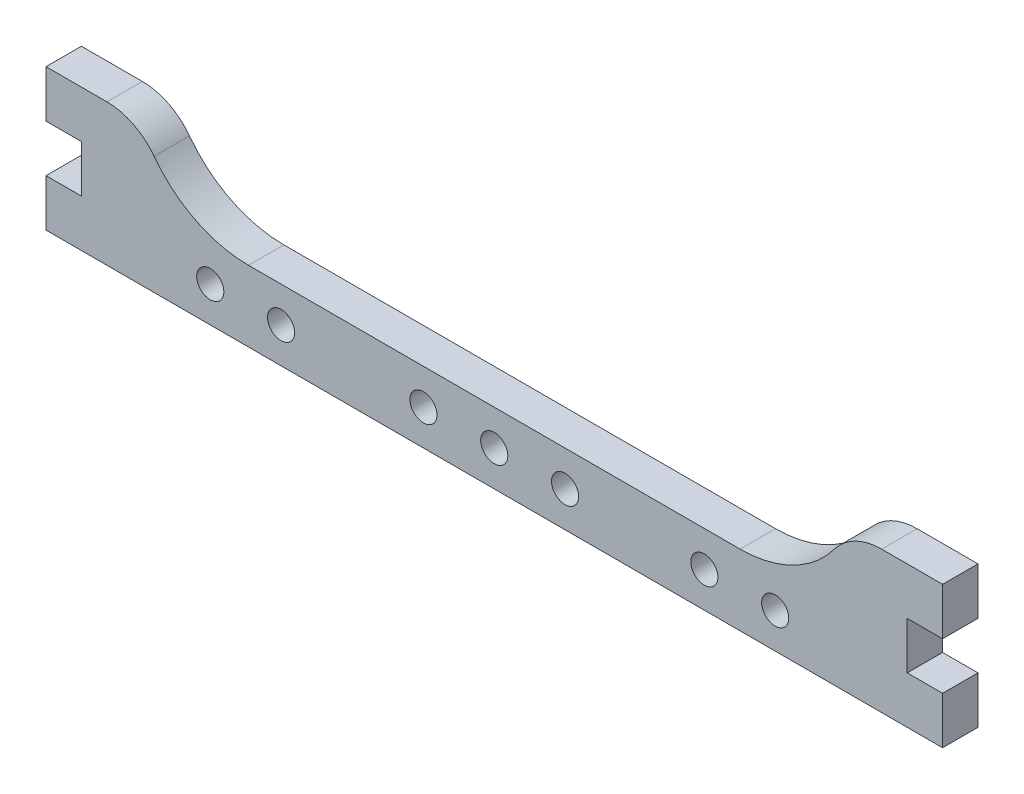
SolidWorks part; units mm, degrees
ref_plane "Front Plane" through (0, 0, 0) normal (0, 0, 1) x (1, 0, 0)
ref_plane "Top Plane" through (0, 0, 0) normal (0, 1, 0) x (1, 0, 0)
ref_plane "Right Plane" through (0, 0, 0) normal (1, 0, 0) x (0, 0, -1)
sketch "Sketch1" plane through (0, 0, 0) normal (0, 0, 1) x (1, 0, 0)
  line L1 (-35, 0) -> (35, 0)
  line L2 (-35, 0) -> (-35, 12)
  line L3 (-35, 12) -> (35, 12)
  line L4 (35, 0) -> (35, 12)
  point P4 (0, 0)
  dimension "D1" = 70
  dimension "D2" = 12
extrude "Boss-Extrude1" add sketch "Sketch1" along normal mid plane 3
sketch "Sketch2" plane through (0, 0, 1.5) normal (0, 0, 1) x (1, 0, 0)
  line L0 (-30, 12) -> (-30, 6)
  line L1 (35, 12) -> (-35, 12) construction
  line L2 (-30, 6) -> (30, 6)
  line L3 (30, 6) -> (30, 12)
  line L4 (-35, 0) -> (35, 0) construction
  point P8 (0, 6)
  line M7 (35, 12) -> (-35, 12)
  dimension "D1" = 6
  dimension "D2" = 60
extrude "Cut-Extrude1" cut sketch "Sketch2" against normal through all contours L2 L3 L0 M7 region at (0, 9, 1.5)
fillet "Fillet1" radius 10 2 edges at (30, 6, 0) (-30, 6, 0)
fillet "Fillet2" radius 5 2 edges at (30, 12, 0) (-30, 12, 0)
sketch "Sketch3" plane through (0, 0, 1.5) normal (0, 0, 1) x (1, 0, 0)
  line L0 (0, 0) -> (0, 6) construction
  line L1 (35, 12) -> (38, 12)
  line L2 (35, 12) -> (35, 8)
  line L3 (35, 8) -> (38, 8)
  line L4 (38, 12) -> (38, 8)
  line L5 (35, 0) -> (38, 0)
  line L6 (35, 0) -> (35, 4)
  line L7 (35, 4) -> (38, 4)
  line L8 (38, 0) -> (38, 4)
  line L9 (-20.8348, 6) -> (20.8348, 6) construction
  line L10 (-38, 0) -> (-38, 4)
  line L11 (-35, 4) -> (-38, 4)
  line L12 (-35, 0) -> (-35, 4)
  line L13 (-35, 0) -> (-38, 0)
  line L14 (-38, 12) -> (-38, 8)
  line L15 (-35, 8) -> (-38, 8)
  line L16 (-35, 12) -> (-35, 8)
  line L17 (-35, 12) -> (-38, 12)
  dimension "D1" = 4
  dimension "D2" = 4
  dimension "D3" = 3
extrude "Boss-Extrude2" add sketch "Sketch3" against normal up to vertex (3 mm away) up to point (-20.8348, 6, -1.5)
sketch "Sketch4" plane through (0, 0, 1.5) normal (0, 0, 1) x (1, 0, 0)
  line L0 (-38, 0) -> (38, 0) construction
  line L1 (25, 4) -> (32, 4)
  line L2 (25, 4) -> (25, 0)
  line L3 (25, 0) -> (32, 0)
  line L4 (32, 4) -> (32, 0)
  line L5 (25, 4) -> (32, 0) construction
  line L6 (25, 0) -> (32, 4) construction
  line L7 (35, 4) -> (35, 8) construction
  line L8 (0, 0) -> (0, 6) construction
  line L9 (-20.8348, 6) -> (20.8348, 6) construction
  line L10 (-25, 0) -> (-32, 4) construction
  line L11 (-25, 4) -> (-32, 0) construction
  line L12 (-32, 4) -> (-32, 0)
  line L13 (-25, 0) -> (-32, 0)
  line L14 (-25, 4) -> (-25, 0)
  line L15 (-25, 4) -> (-32, 4)
  point P0 (28.5, 2)
  point P17 (-28.5, 2)
  dimension "D1" = 7
  dimension "D2" = 4
  dimension "D3" = 3
extrude "Cut-Extrude2" [suppressed] cut sketch "Sketch4" against normal through all
sketch "Sketch5" plane through (0, 0, 1.5) normal (0, 0, 1) x (1, 0, 0)
  line L0 (-20.8348, 6) -> (20.8348, 6) construction
  circle A0 centre (-0.0055, 3) radius 1.15
  circle A1 centre (-6.0075, 2.995) radius 1.15
  circle A2 centre (5.9982, 2.9979) radius 1.15
  circle A3 centre (17.8062, 2.9894) radius 1.15
  circle A4 centre (23.8099, 2.9873) radius 1.15
  circle A5 centre (-24.076, 2.9979) radius 1.15
  circle A6 centre (-18.0722, 2.9958) radius 1.15
  point P5 (0, 0)
  point P24 (0, 0)
extrude "Cut-Extrude4" cut sketch "Sketch5" against normal blind 10 contours A5 | A6 | A1 | A0 | A3 | A4 | A2
